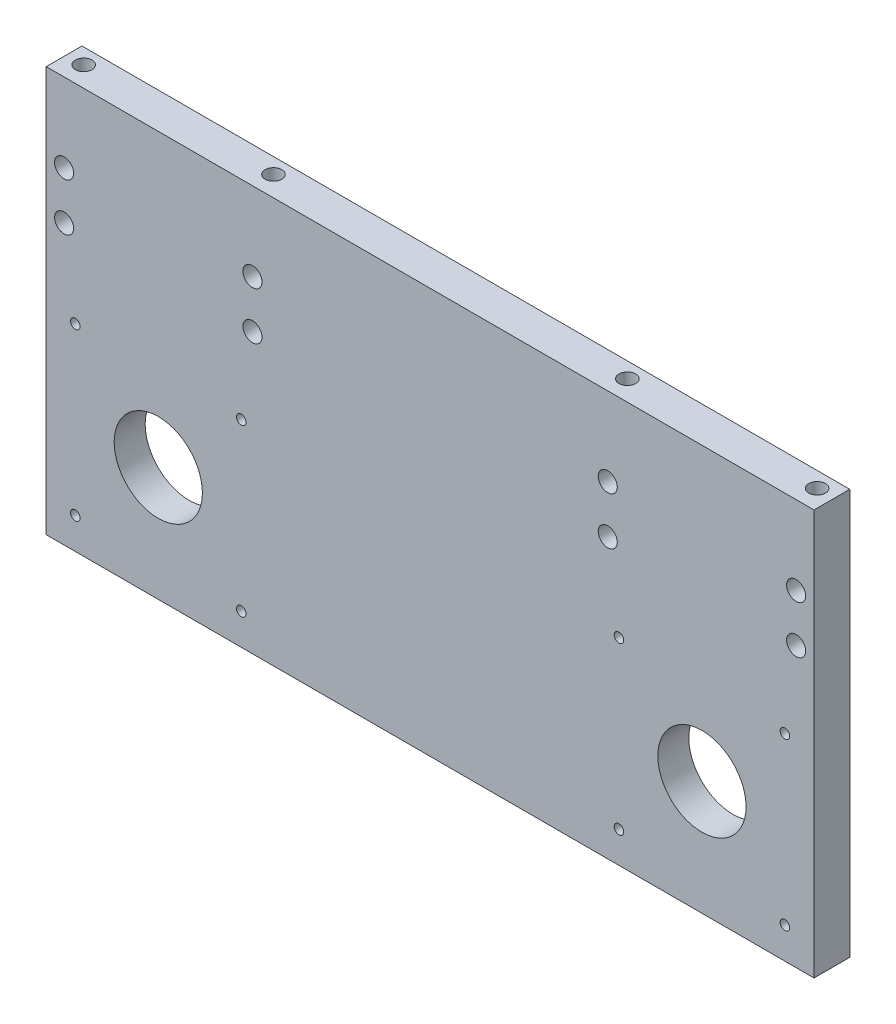
SolidWorks part; units mm, degrees
ref_plane "Płaszczyzna przednia" through (0, 0, 0) normal (0, 0, 1) x (1, 0, 0)
ref_plane "Płaszczyzna górna" through (0, 0, 0) normal (0, 1, 0) x (1, 0, 0)
ref_plane "Płaszczyzna prawa" through (0, 0, 0) normal (1, 0, 0) x (0, 0, -1)
sketch "Szkic1" plane through (0, 0, 0) normal (0, 0, 1) x (1, 0, 0)
  line L1 (161, -85) -> (-161, -85)
  line L2 (161, -85) -> (161, 85)
  line L3 (161, 85) -> (-161, 85)
  line L4 (-161, -85) -> (-161, 85)
  line L5 (161, -85) -> (-161, 85) construction
  line L6 (161, 85) -> (-161, -85) construction
  point P0 (0, 0)
  dimension "D1" = 322
  dimension "D2" = 170
extrude "Dodanie-wyciągnięcie1" add sketch "Szkic1" along normal blind 15
sketch "Szkic2" plane through (0, 0, 15) normal (0, 0, 1) x (1, 0, 0)
  line L2 (-161, -85) -> (161, -85) construction
  line L7 (-161, 85) -> (-161, -85) construction
  circle A1 centre (-148.8, -71.87) radius 2
  dimension "D1" = 13.13
  dimension "D2" = 12.2
  dimension "D5" = 4
extrude "Wytnij-wyciągnięcie2" cut sketch "Szkic2" against normal blind 17.75 contours A1 region at (-148.8, -71.87, 15)
pattern_linear "Szyk liniowy1" count 2 spacing 69.6 along (1, 0, 0) count 2 spacing 69.6 along (0, 1, 0) of "Wytnij-wyciągnięcie2"
sketch "Szkic5" plane through (0, 0, 0) normal (0, 0, -1) x (-1, 0, 0)
  line L1 (161, -85) -> (-161, -85) construction
  line L2 (161, 85) -> (161, -85) construction
  circle A1 centre (114, -37.07) radius 37.5
  dimension "D1" = 47.93
  dimension "D5" = 75
  dimension "D2" = 47
extrude "Wytnij-wyciągnięcie3" cut sketch "Szkic5" against normal blind 2 contours A1 region at (-114, -37.07, 0)
sketch "Szkic7" plane through (0, 0, 2) normal (0, 0, -1) x (-1, 0, 0)
  circle A3 centre (114, -37.07) radius 18.5
  dimension "D1" = 37
extrude "Wytnij-wyciągnięcie4" cut sketch "Szkic7" against normal blind 17.75 contours A3 region at (-114, -37.07, 2)
sketch "Szkic10" plane through (0, 0, 15) normal (0, 0, 1) x (1, 0, 0)
  line L0 (161, 85) -> (-161, 85) construction
  line L1 (-161, 85) -> (-161, -85) construction
  circle A0 centre (-153.5, 52) radius 4
  circle A1 centre (-153.5, 32) radius 4
  dimension "D1" = 53
  dimension "D3" = 8
  dimension "D4" = 8
  dimension "D2" = 20
  dimension "D5" = 7.5
extrude "Wytnij-wyciągnięcie7" cut sketch "Szkic10" against normal through all
pattern_linear "Szyk liniowy3" count 2 spacing 79 along (1, 0, 0) of "Wytnij-wyciągnięcie7"
pattern_linear "Szyk liniowy2" count 2 spacing 228 along (1, 0, 0) of "Wytnij-wyciągnięcie2", "Szyk liniowy1", "Wytnij-wyciągnięcie3", "Wytnij-wyciągnięcie4", "Szyk liniowy3"
sketch "Szkic8" plane through (0, 85, 0) normal (0, 1, 0) x (1, 0, 0)
  line L0 (-161, -15) -> (-161, 0) construction
  line L1 (161, -15) -> (-161, -15) construction
  line L2 (161, -15) -> (161, 0) construction
  line L3 (161, -15) -> (-161, -15) construction
  circle A0 centre (-153.8, -6.5) radius 4
  circle A1 centre (153.8, -6.5) radius 4
  dimension "D1" = 7.2
  dimension "D3" = 8
  dimension "D6" = 8
  dimension "D2" = 8.5
  dimension "D4" = 7.2
  dimension "D5" = 8.5
extrude "Wytnij-wyciągnięcie5" [suppressed] cut sketch "Szkic8" against normal blind 20
sketch "Szkic11" plane through (0, 0, 15) normal (0, 0, 1) x (1, 0, 0)
  line L0 (161, 85) -> (-161, 85) construction
  line L1 (161, -85) -> (161, 85) construction
  circle A0 centre (153.5, 32) radius 4
  circle A1 centre (153.5, 52) radius 4
  dimension "D1" = 53
  dimension "D2" = 8
  dimension "D3" = 8
  dimension "D4" = 7.5
  dimension "D5" = 20
extrude "Wytnij-wyciągnięcie8" [suppressed] cut sketch "Szkic11" against normal through all
hole_wizard "Otwór gwintowany M8x1.01" positions "Szkic12" profile "Szkic13" tap size "M8x1.0" standard "Ansi Metric"
sketch "Szkic12" plane through (0, 85, 0) normal (0, 1, 0) x (1, 0, 0)
  line L0 (-161, -6.5) -> (161, -6.5) construction
  line L1 (-161, -15) -> (-161, 0) construction
  line L2 (161, -15) -> (161, 0) construction
  line L5 (161, -15) -> (-161, -15) construction
  point P0 (-153.8, -6.5)
  point P2 (-74.2, -6.5)
  point P4 (74.2, -6.5)
  point P6 (153.8, -6.5)
  dimension "D1" = 8.5
  dimension "D2" = 7.2
  dimension "D3" = 7.2
  dimension "D4" = 79.6
  dimension "D5" = 79.6
sketch "Szkic13" plane through (-153.8, 85, 6.5) normal (1, 0, 0) x (0, 0, 1)
  line L0 (0, 0) -> (0, 23.103)
  line L1 (0, 23.103) -> (3.5, 21)
  line L2 (3.5, 21) -> (3.5, 0)
  line L5 (3.5, 0) -> (0, 0)
  line L10 (0, 23.103) -> (-3.5, 21) construction
  line L11 (0, -6.35) -> (0, 107.95) construction
  dimension "Średnica wiertła gwintu" = 7
  dimension "Głębokość otworu gwintowanego" = 21
  dimension "Kąt wiertła" = 118
cosmetic thread "Gwint otworu1" parameters "D1"=16, "D2"=8
cosmetic thread "Gwint otworu2" parameters "D1"=16, "D2"=8
cosmetic thread "Gwint otworu3" parameters "D1"=16, "D2"=8
cosmetic thread "Gwint otworu4" parameters "D1"=16, "D2"=8
